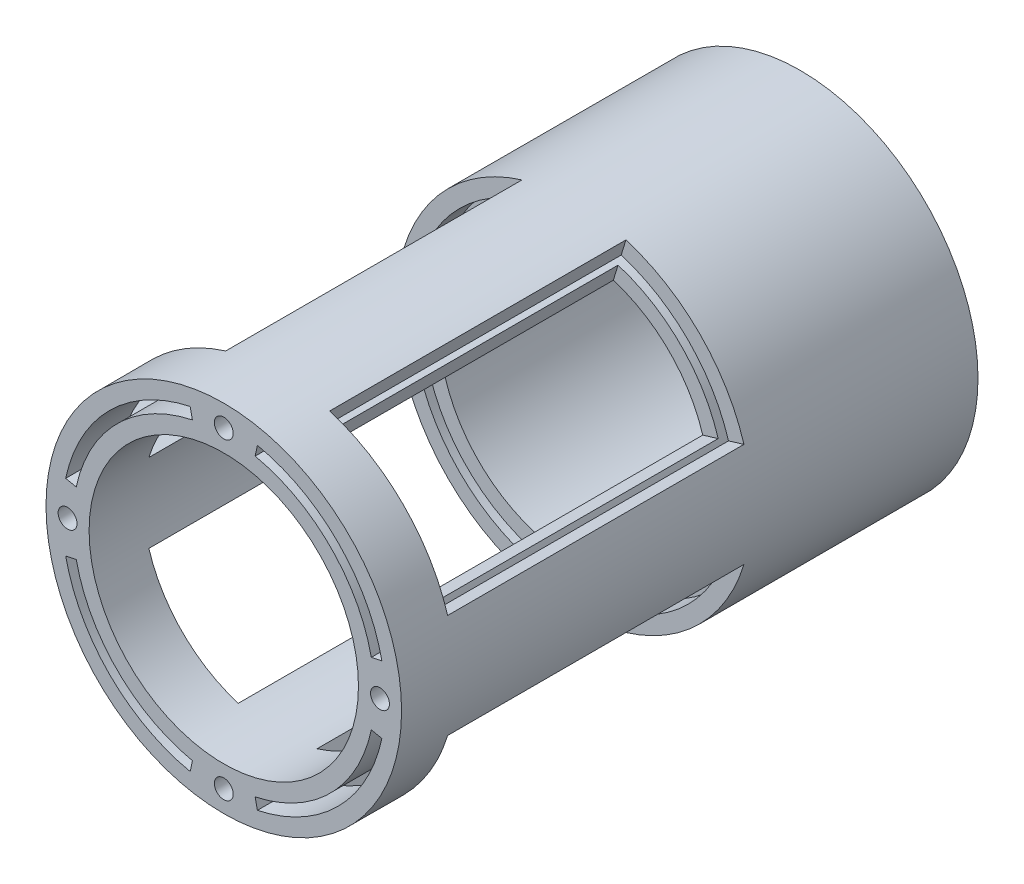
SolidWorks part; units mm, degrees
ref_plane "Alzado" through (0, 0, 0) normal (0, 0, 1) x (1, 0, 0)
ref_plane "Planta" through (0, 0, 0) normal (0, 1, 0) x (1, 0, 0)
ref_plane "Vista lateral" through (0, 0, 0) normal (1, 0, 0) x (0, 0, -1)
sketch "Croquis1" plane through (0, 0, 0) normal (0, 0, 1) x (1, 0, 0)
  circle A0 centre (0, 0) radius 33
  circle A1 centre (0, 0) radius 25
  dimension "D1" = 66
  dimension "D2" = 8
extrude "Boss-Extrude1" add sketch "Croquis1" along normal blind 107
sketch "Sketch1" plane through (0, 0, 0) normal (0, 0, -1) x (-1, 0, 0)
  line L0 (0, 0) -> (11.3818, 0) construction
  circle A0 centre (-29, 0) radius 1.5
  circle A1 centre (0, 29) radius 1.5
  circle A2 centre (29, 0) radius 1.5
  circle A3 centre (0, -29) radius 1.5
  circle A7 centre (0, 0) radius 29 construction
  circle A8 centre (0, 0) radius 25 construction
  point P17 (0, 0)
  dimension "D1" = 4
  dimension "D2" = 3
  dimension "D3" = 0
  dimension "D4" = 4
extrude "Cut-Extrude1" cut sketch "Sketch1" against normal blind 5
sketch "Sketch2" plane through (0, 0, 107) normal (0, 0, 1) x (1, 0, 0)
  circle A0 centre (-29, 0) radius 1.75
  circle A2 centre (0, 0) radius 29 construction
  circle A3 centre (0, 0) radius 25 construction
  circle A4 centre (0, 29) radius 1.75
  circle A5 centre (29, 0) radius 1.75
  circle A6 centre (0, -29) radius 1.75
  point P16 (0, 0)
  dimension "D1" = 4
  dimension "D2" = 3.5
  dimension "D3" = 4
extrude "Cut-Extrude2" cut sketch "Sketch2" against normal blind 5
sketch "Croquis2" plane through (0, 0, 107) normal (0, 0, 1) x (1, 0, 0)
  line L0 (0, 0) -> (-6.2374, -29.3444) construction
  line L1 (0, 0) -> (-29.3444, -6.2374) construction
  line L2 (0, 0) -> (0, -29) construction
  line L3 (0, 0) -> (-29, 0) construction
  line L4 (-29.3444, -6.2374) -> (-27.3881, -5.8215)
  line L5 (-6.2374, -29.3444) -> (-5.8215, -27.3881)
  line L6 (-29.3444, 6.2374) -> (-27.3881, 5.8215)
  line L7 (-6.2374, 29.3444) -> (-5.8215, 27.3881)
  line L8 (6.2374, 29.3444) -> (5.8215, 27.3881)
  line L9 (29.3444, 6.2374) -> (27.3881, 5.8215)
  line L10 (29.3444, -6.2374) -> (27.3881, -5.8215)
  line L11 (6.2374, -29.3444) -> (5.8215, -27.3881)
  circle A0 centre (0, 0) radius 28 construction
  circle A1 centre (0, 0) radius 30 construction
  circle A2 centre (0, 0) radius 25 construction
  circle A3 centre (0, 0) radius 33 construction
  arc A4 (-6.2374, -29.3444) -> (-29.3444, -6.2374) centre (0, 0) cw
  arc A5 (-5.8215, -27.3881) -> (-27.3881, -5.8215) centre (0, 0) cw
  arc A6 (-29.3444, 6.2374) -> (-6.2374, 29.3444) centre (0, 0) cw
  arc A7 (-27.3881, 5.8215) -> (-5.8215, 27.3881) centre (0, 0) cw
  arc A8 (6.2374, 29.3444) -> (29.3444, 6.2374) centre (0, 0) cw
  arc A9 (5.8215, 27.3881) -> (27.3881, 5.8215) centre (0, 0) cw
  arc A10 (29.3444, -6.2374) -> (6.2374, -29.3444) centre (0, 0) cw
  arc A11 (27.3881, -5.8215) -> (5.8215, -27.3881) centre (0, 0) cw
  point P32 (0, 0)
  dimension "D1" = 3
  dimension "D2" = 3
  dimension "D3" = 12
  dimension "D4" = 12
  dimension "D5" = 4
extrude "Cortar-Extruir1" cut sketch "Croquis2" against normal blind 70
ref_axis "Eje1" through (0, 0, 107) along (0, 0, -1)
ref_plane "Plano2" through (0, 0, 0) normal (0.9563, -0.2924, 0) x (0, 0, -1)
sketch "Croquis4" plane through (0, 0, 0) normal (0.9563, -0.2924, 0) x (0, 0, -1)
  line L0 (-97, 33) -> (-97, 30)
  line L1 (0, 33) -> (-107, 33) construction
  line L2 (-97, 25) -> (-42, 25)
  line L3 (-42, 25) -> (-42, 28)
  line L4 (-42, 33) -> (-97, 33)
  line L5 (-97, 29) -> (-42, 29) construction
  line L6 (-107, 33) -> (-107, -33) construction
  line L7 (-107, 30) -> (-97, 30)
  line L8 (-37, 30) -> (-37, 28)
  line L9 (-37, 28) -> (-42, 28)
  line L10 (-107, 28) -> (-107, 30)
  line L11 (-97, 28) -> (-107, 28)
  line L12 (-97, 28) -> (-97, 25)
  line L13 (-42, 30) -> (-37, 30)
  line L14 (-42, 30) -> (-42, 33)
  dimension "D1" = 8
  dimension "D2" = 65
  dimension "D3" = 3
  dimension "D4" = 3
  dimension "D5" = 5
  dimension "D6" = 10
revolve "Cortar-Revolución2" cut sketch "Croquis4" angle 56 about axis through (0, 0, 107) along (0, 0, -1)
pattern_circular "MatrizC2" count 4 every 90 about axis through (0, 0, 107) along (0, 0, -1) of "Cortar-Revolución2"
